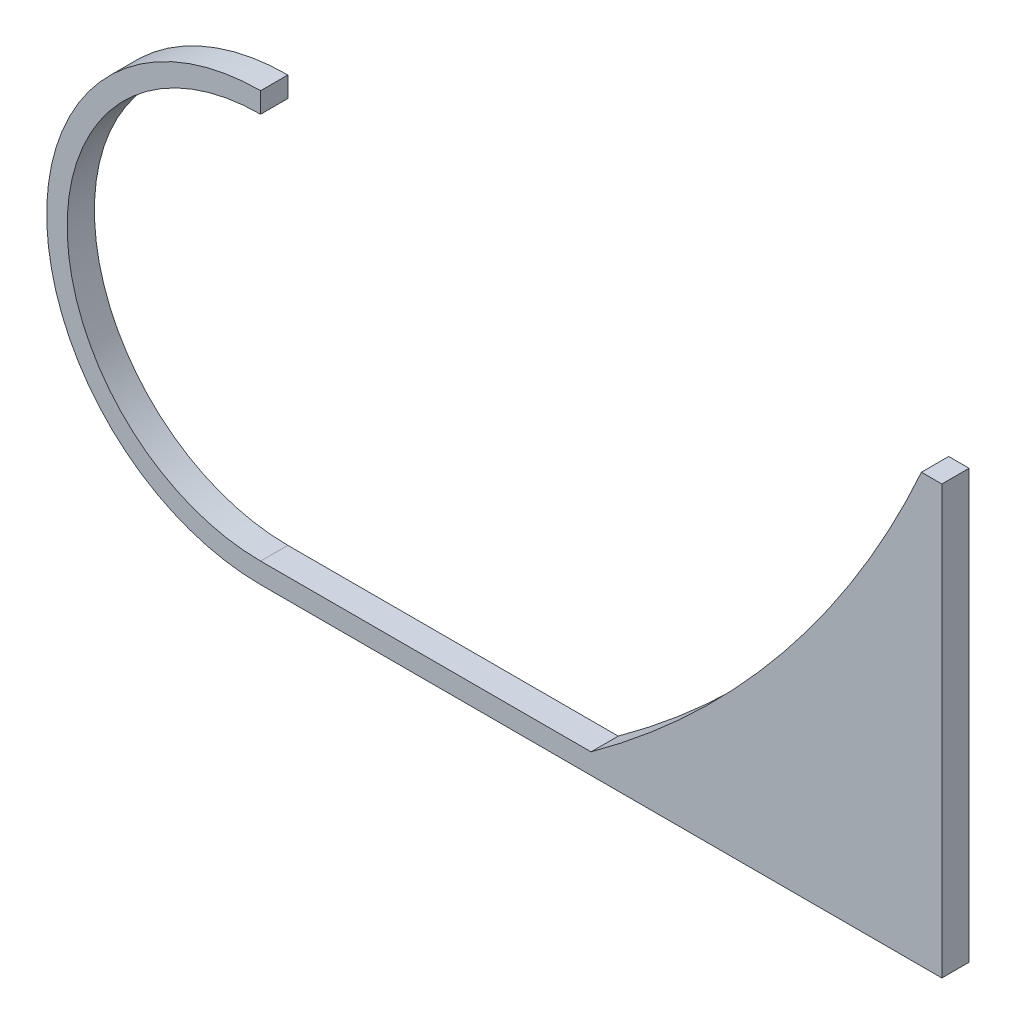
SolidWorks part; units mm, degrees
ref_plane "Front Plane" through (0, 0, 0) normal (0, 0, 1) x (1, 0, 0)
ref_plane "Top Plane" through (0, 0, 0) normal (0, 1, 0) x (1, 0, 0)
ref_plane "Right Plane" through (0, 0, 0) normal (1, 0, 0) x (0, 0, -1)
sketch "Sketch1" plane through (0, 0, 0) normal (0, 0, 1) x (1, 0, 0)
  circle A0 centre (0, 0) radius 19.939
  dimension "D1" = 39.878
extrude "circle extrude" add sketch "Sketch1" along normal blind 2.54
sketch "Sketch3" plane through (0, 0, 0) normal (1, 0, 0) x (0, 0, -1)
  line L0 (0, 21.9329) -> (0, -21.9329) construction
  line L1 (-2.54, 19.939) -> (0, 19.939)
  line L2 (-2.54, 19.939) -> (-2.54, -19.939)
  line L3 (-2.54, -19.939) -> (0, -19.939)
  line L4 (0, 19.939) -> (0, -19.939)
  line L5 (-2.54, -19.939) -> (0, -19.939) construction
extrude "rectangle extrude" add sketch "Sketch3" along normal blind 63.5
sketch "Sketch2" plane through (0, 0, 2.54) normal (0, 0, 1) x (1, 0, 0)
  circle A0 centre (0, 0) radius 18.034
  dimension "D1" = 36.068
extrude "circle cut" cut sketch "Sketch2" against normal blind 2.54
sketch "Sketch6" plane through (0, 0, 2.54) normal (0, 0, 1) x (1, 0, 0)
  line L1 (61.595, -18.034) -> (61.595, 19.939)
  line L3 (0, -18.034) -> (0, 19.939)
  line L4 (0, -18.034) -> (61.595, -18.034)
  line L5 (63.5, -19.939) -> (0, -19.939) construction
  line L6 (0, 19.939) -> (61.595, 19.939)
  line L8 (63.5, 19.939) -> (63.5, -19.939) construction
  line L9 (63.5, 19.939) -> (0, 19.939) construction
  arc A0 (0, 19.939) -> (0, -19.939) centre (0, 0) ccw construction
  point P5 (61.595, 0.9525)
  point P12 (0, 0.9525)
  point P14 (30.7975, 19.939)
  point P17 (-19.939, 0)
  dimension "D1" = 1.905
  dimension "D2" = 1.905
  dimension "D3" = 19.939
extrude "rectangle cut" cut sketch "Sketch6" against normal through all
sketch "Sketch9" plane through (0, 0, 2.54) normal (0, 0, 1) x (1, 0, 0)
  line L0 (0, -18.034) -> (61.595, -18.034) construction
  line L1 (61.595, 19.939) -> (61.595, -18.034)
  line L2 (61.595, -18.034) -> (30.7975, -18.034)
  arc A0 (30.7975, -18.034) -> (61.595, 19.939) centre (-24.6623, 58.4214) ccw
  dimension "D1" = 94.4522
extrude "Boss-Extrude1" add sketch "Sketch9" against normal blind 2.54 separate body
combine bodies "Combine1" operation type add bodies to combine 105 106
